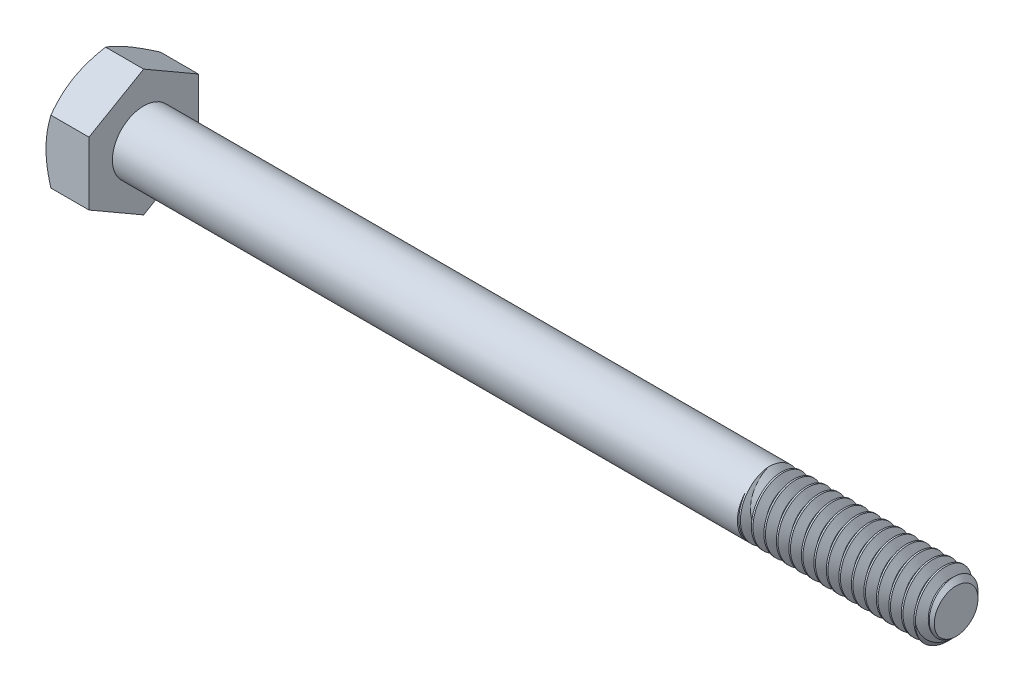
SolidWorks part; units mm, degrees
ref_plane "Front Plane" through (0, 0, 0) normal (0, 0, 1) x (1, 0, 0)
ref_plane "Top Plane" through (0, 0, 0) normal (0, 1, 0) x (1, 0, 0)
ref_plane "Right Plane" through (0, 0, 0) normal (1, 0, 0) x (0, 0, -1)
sketch "Sketch1" plane through (0, 0, 0) normal (0, 0, 1) x (1, 0, 0)
  line L0 (-43.4578, 0) -> (43.4578, 0) construction
  line L1 (43.4578, 3.175) -> (43.4578, -3.175) construction
  line L2 (-39.0922, 5.5562) -> (-39.0922, -5.5562) construction
  line L3 (-43.4578, 5.5562) -> (-43.4578, -5.5562) construction
  point P9 (-39.0922, 0)
  point P10 (39.0128, -3.175)
  dimension "D1" = 4.445
  dimension "Screw Dia" = 6.35
  dimension "Hex" = 11.1125
  dimension "Head Ht" = 4.3656
  dimension "Screw Lenght" = 82.55
ref_plane "Plane2" through (43.4578, 0, 0) normal (1, 0, 0) x (0, 0, -1)
sketch "Sketch5" plane through (43.4578, 0, 0) normal (1, 0, 0) x (0, 0, -1)
  circle A0 centre (0, 0) radius 3.175
extrude "Boss-Extrude3" add sketch "Sketch5" against normal up to vertex (82.55 mm away) up to point (-39.0922, 0, 0)
sketch "Sketch9" plane through (43.4578, 0, 0) normal (1, 0, 0) x (0, 0, -1)
  circle A1 centre (0, 0) radius 3.175
  circle A2 centre (0, 0) radius 3.175
  dimension "D1" = 0
curve "Helix/Spiral1" pitch 1.27 height 20.32 turns 16 parameters "Pitch"=1.27
chamfer "Chamfer1" distance 0.9525 angle 45 1 edges at (43.4578, 0, -3.175)
sketch "Sketch10" plane through (0, 0, 0) normal (0, 0, 1) x (1, 0, 0)
  line L0 (43.4578, 3.175) -> (43.9341, 2.3501)
  line L1 (43.9341, 2.3501) -> (44.0928, 2.3501)
  line L2 (44.0928, 2.3501) -> (44.5691, 3.175)
  line L3 (43.4578, 3.175) -> (44.5691, 3.175)
  line L4 (44.0134, 3.175) -> (44.0134, 2.3501) construction
  line L5 (43.6959, 2.7626) -> (44.3309, 2.7626) construction
  dimension "D1" = 60
  dimension "D2" = 0.1588
  dimension "D3" = 0.635
sweep "Cut-Sweep1" cut profiles "Sketch10" path "Helix/Spiral1"
sketch "Sketch11" plane through (0, 0, 0) normal (0, 0, 1) x (1, 0, 0)
  line L0 (-39.0922, 3.175) -> (-39.0922, 0)
  line L1 (-39.0922, 0) -> (27.5828, 0)
  line L3 (27.5828, 0) -> (24.4078, 3.175)
  line L4 (-39.0922, 3.175) -> (24.4078, 3.175)
  dimension "D1" = 45
  dimension "MIn Thread" = 19.05
revolve "Revolve1" add sketch "Sketch11" angle 360 about L1
sketch "Sketch6" plane through (-39.0922, 0, 0) normal (-1, 0, 0) x (0, 0, 1)
  line L0 (0, 5.5562) -> (0, -5.5562) construction
  line L1 (5.5563, 3.2079) -> (0, 6.4158)
  line L2 (0, 6.4158) -> (-5.5562, 3.2079)
  line L3 (-5.5562, 3.2079) -> (-5.5562, -3.2079)
  line L4 (-5.5562, -3.2079) -> (0, -6.4158)
  line L5 (0, -6.4158) -> (5.5563, -3.2079)
  line L6 (5.5563, -3.2079) -> (5.5563, 3.2079)
  circle A0 centre (0, 0) radius 5.5562 construction
extrude "Boss-Extrude4" add sketch "Sketch6" along normal up to vertex (4.3656 mm away) up to point (-43.4578, -5.5562, 0)
sketch "Sketch7" plane through (-43.4578, 0, 0) normal (-1, 0, 0) x (0, 0, 1)
  circle A0 centre (0, 0) radius 5.5562 construction
  circle A1 centre (0, 0) radius 5.5562
sketch "Sketch8" plane through (-43.4578, 0, 0) normal (-1, 0, 0) x (0, 0, 1)
  circle A0 centre (0, 0) radius 5.5562 construction
  circle A1 centre (0, 0) radius 5.5562
extrude "Cut-Extrude3" cut sketch "Sketch8" against normal through all draft 60 flip side to cut
sketch "Sketch12" plane through (-43.4578, 0, 0) normal (-1, 0, 0) x (0, 0, 1)
  line L0 (0, 4.2783) -> (0, 2.3892) construction
  line L1 (0.1667, 4.2783) -> (0.1667, 2.3892)
  line L2 (-0.1667, 4.2783) -> (-0.1667, 2.3892)
  line L3 (0, 3.175) -> (0, -3.175) construction
  arc A0 (0.1667, 4.2783) -> (-0.1667, 4.2783) centre (0, 4.2783) ccw
  arc A1 (-0.1667, 2.3892) -> (0.1667, 2.3892) centre (0, 2.3892) ccw
  circle A3 centre (0, 0) radius 2.2225 construction
  circle A4 centre (0, 0) radius 4.445 construction
  point P2 (0, 3.3337)
  dimension "D1" = 4.445
  dimension "D3" = 8.89
  dimension "D2" = 0.3334
extrude "Cut-Extrude4" cut sketch "Sketch12" against normal blind 0.254
pattern_circular "CirPattern1" count 3 over 360 about axis through (0, 0, 0) along (1, 0, 0) of "Cut-Extrude4"
equation "\"D2@Sketch10\" = \"Pitch@Helix/Spiral1\"*.125"
equation "\"D3@Sketch10\" = \"Pitch@Helix/Spiral1\"*.5"
equation "\"D3@Helix/Spiral1\" = \"MIn Thread@Sketch11\"+\"Pitch@Helix/Spiral1\""
equation "\"D1@Chamfer1\" = \"Pitch@Helix/Spiral1\"*.75"
equation "\"D1@Sketch12\" = \"Hex@Sketch1\"*.4"
equation "\"D3@Sketch12\" = \"Hex@Sketch1\"*.8"
equation "\"D2@Sketch12\" = \"Hex@Sketch1\"*.03"
equation "\"D1@Sketch1\" = \"Pitch@Helix/Spiral1\"*3.5"
